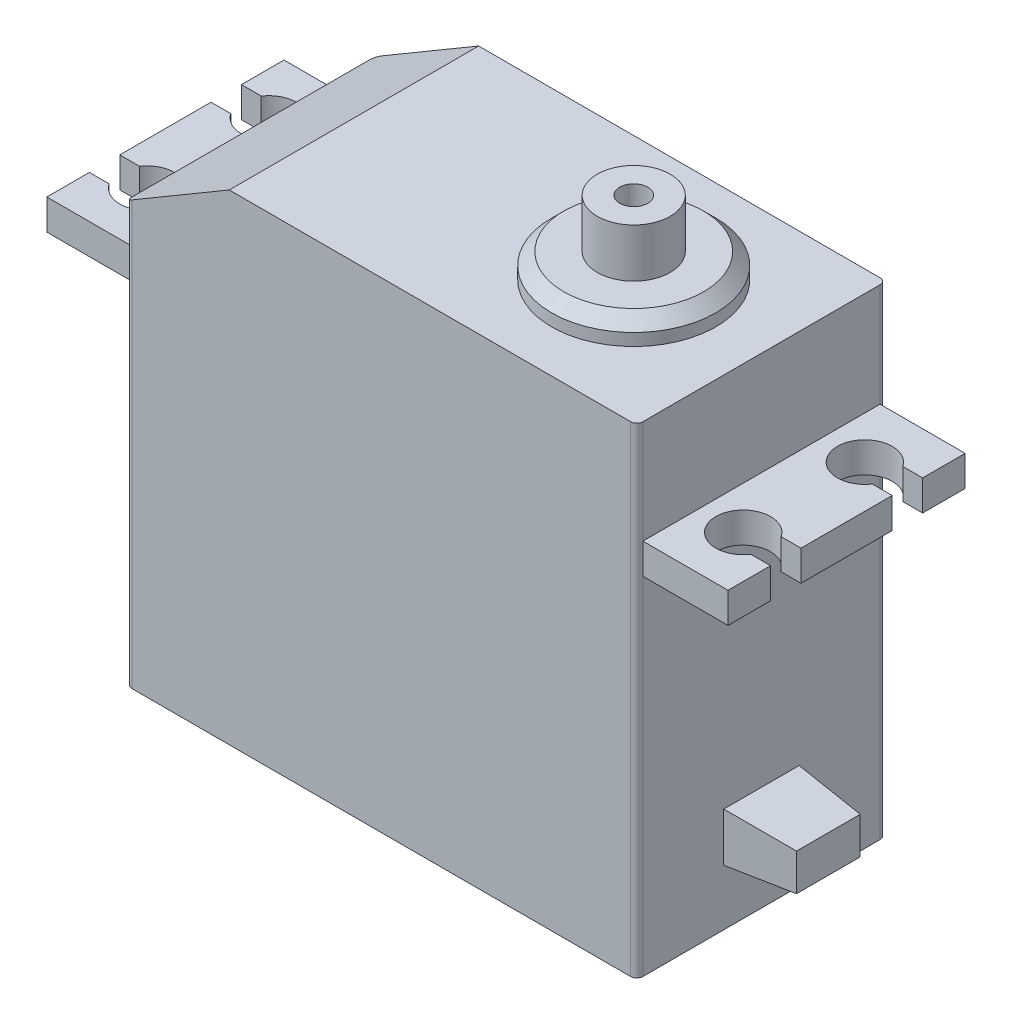
SolidWorks part; units mm, degrees
ref_plane "Front Plane" through (0, 0, 0) normal (0, 0, 1) x (1, 0, 0)
ref_plane "Top Plane" through (0, 0, 0) normal (0, 1, 0) x (1, 0, 0)
ref_plane "Right Plane" through (0, 0, 0) normal (1, 0, 0) x (0, 0, -1)
sketch "Sketch1" plane through (0, 0, 0) normal (0, 1, 0) x (1, 0, 0)
  line L1 (-21, -10.25) -> (21, -10.25)
  line L2 (-21, -10.25) -> (-21, 10.25)
  line L3 (-21, 10.25) -> (21, 10.25)
  line L4 (21, -10.25) -> (21, 10.25)
  point P4 (21, 0)
  point P5 (0, 10.25)
  dimension "D1" = 20.5
  dimension "D2" = 42
extrude "Boss-Extrude1" add sketch "Sketch1" along normal blind 39.5
sketch "Sketch2" plane through (0, 0, 10.25) normal (0, 0, 1) x (1, 0, 0)
  line L0 (-28, 31) -> (28, 31) construction
  line L1 (-21, 39.5) -> (21, 39.5) construction
  line L2 (0, 39.5) -> (0, 0) construction
  line L3 (-21, 0) -> (21, 0) construction
  line L5 (-28, 31) -> (28, 31)
  line L6 (-28, 31) -> (-28, 28.5)
  line L7 (-28, 28.5) -> (28, 28.5)
  line L8 (28, 31) -> (28, 28.5)
  point P8 (0, 31)
  dimension "D1" = 8.5
  dimension "D2" = 56
  dimension "D3" = 2.5
extrude "Boss-Extrude2" add sketch "Sketch2" against normal offset from surface (19.5 mm away) 0.5 from offset 0.5 up to face at (0, 19.75, -10.25) offset against normal yes
sketch "Sketch3" plane through (0, 31, 0) normal (0, 1, 0) x (1, 0, 0)
  line L1 (24.5, 5) -> (-24.5, 5) construction
  line L2 (0, 10.25) -> (0, -10.25) construction
  line L3 (21, 10.25) -> (-21, 10.25) construction
  line L4 (-21, -10.25) -> (21, -10.25) construction
  line L5 (-28, 0) -> (28, 0) construction
  line L6 (-28, 9.75) -> (-28, -9.75) construction
  line L7 (28, 9.75) -> (28, -9.75) construction
  line L8 (26.3708, 3.75) -> (28, 3.75)
  line L10 (26.3708, 6.25) -> (28, 6.25)
  line L11 (28, 3.75) -> (28, 6.25)
  arc A0 (26.3708, 6.25) -> (26.3708, 3.75) centre (24.5, 5) ccw
  circle A1 centre (-24.5, 5) radius 2.25 construction
  point P18 (0, 5)
  dimension "D1" = 4.5
  dimension "D2" = 49
  dimension "D3" = 5
  dimension "D4" = 2.5
extrude "Cut-Extrude1" cut sketch "Sketch3" against normal blind 40
mirror "Mirror1" about plane through (0, 0, 0) normal (0, 0, 1) of "Cut-Extrude1"
mirror "Mirror2" about plane through (0, 0, 0) normal (1, 0, 0) of "Mirror1"
sketch "Sketch4" plane through (0, 0, 10.25) normal (0, 0, 1) x (1, 0, 0)
  line L0 (-21, 34.5) -> (-12.5, 39.5)
  line L1 (-21, 39.5) -> (-21, 0) construction
  line L2 (-21, 39.5) -> (21, 39.5) construction
  line L3 (-21, 34.5) -> (-24.4769, 34.5)
  line L4 (-24.4769, 34.5) -> (-24.4769, 42.3263)
  line L5 (-24.4769, 42.3263) -> (-12.5, 42.3263)
  line L6 (-12.5, 42.3263) -> (-12.5, 39.5)
  line L7 (-21, 31) -> (-28, 31) construction
  dimension "D1" = 3.5
  dimension "D2" = 33.5
extrude "Cut-Extrude2" cut sketch "Sketch4" against normal blind 40
sketch "Sketch5" plane through (0, 39.5, 0) normal (0, 1, 0) x (1, 0, 0)
  line L0 (21, -9.75) -> (21, 9.75) construction
  circle A0 centre (10.5, 0) radius 3
  dimension "D1" = 6
  dimension "D2" = 10.5
extrude "Boss-Extrude3" add sketch "Sketch5" along normal blind 6
sketch "Sketch6" plane through (0, 39.5, 0) normal (0, 1, 0) x (1, 0, 0)
  circle A0 centre (10.5, 0) radius 6.75
  dimension "D1" = 13.5
extrude "Boss-Extrude4" add sketch "Sketch6" along normal blind 2
sketch "Sketch7" plane through (0, 45.5, 0) normal (0, 1, 0) x (1, 0, 0)
  circle A0 centre (10.5, 0) radius 1.15
  dimension "D1" = 2.3
extrude "Cut-Extrude3" cut sketch "Sketch7" against normal blind 5
fillet "Fillet1" radius 0.5 4 edges at (-21, 17.25, -10.25) (21, 19.75, -10.25) (21, 19.75, 10.25) (-21, 17.25, 10.25)
sketch "Sketch8" plane through (21, 0, 0) normal (1, 0, 0) x (0, 0, -1)
  line L0 (-9.75, 0) -> (9.75, 0) construction
  line L1 (-3.1, 4.6) -> (3.1, 4.6)
  line L2 (-3.1, 4.6) -> (-3.1, 8.6)
  line L3 (-3.1, 8.6) -> (3.1, 8.6)
  line L4 (3.1, 4.6) -> (3.1, 8.6)
  point P6 (0, 4.6)
  dimension "D1" = 4
  dimension "D2" = 6.2
  dimension "D3" = 4.6
extrude "Boss-Extrude5" add sketch "Sketch8" along normal blind 5.5 draft 5
chamfer "Chamfer1" distance 1 angle 45 1 edges at (10.5, 41.5, 6.75)
sketch "Sketch9" plane through (0, 39.5, 0) normal (0, 1, 0) x (1, 0, 0)
  line B0 (21, -9.75) -> (21, 9.75)
  line B1 (20.5, 10.25) -> (-12.5, 10.25)
  line B2 (-12.5, -10.25) -> (20.5, -10.25)
  line B3 (-12.5, 10.25) -> (-20.5, 10.25)
  line B4 (-21, 9.75) -> (-21, -9.75)
  line B5 (-20.5, -10.25) -> (-12.5, -10.25)
  line B6 (-28, 9.75) -> (-28, 6.25)
  line B7 (-28, 6.25) -> (-26.3708, 6.25)
  line B8 (-26.3708, 3.75) -> (-28, 3.75)
  line B9 (-28, 3.75) -> (-28, -3.75)
  line B10 (-28, -3.75) -> (-26.3708, -3.75)
  line B11 (-26.3708, -6.25) -> (-28, -6.25)
  line B12 (-28, -6.25) -> (-28, -9.75)
  line B13 (-28, -9.75) -> (-21, -9.75)
  line B14 (-21, -9.75) -> (-21, 9.75)
  line B15 (-21, 9.75) -> (-28, 9.75)
  line B16 (28, -9.75) -> (28, -6.25)
  line B17 (28, -6.25) -> (26.3708, -6.25)
  line B18 (26.3708, -3.75) -> (28, -3.75)
  line B19 (28, -3.75) -> (28, 3.75)
  line B20 (28, 3.75) -> (26.3708, 3.75)
  line B21 (26.3708, 6.25) -> (28, 6.25)
  line B22 (28, 6.25) -> (28, 9.75)
  line B23 (28, 9.75) -> (21, 9.75)
  line B24 (21, 9.75) -> (21, -9.75)
  line B25 (21, -9.75) -> (28, -9.75)
  arc B26 (21, 9.75) -> (20.5, 10.25) centre (20.5, 9.75) ccw
  arc B27 (20.5, -10.25) -> (21, -9.75) centre (20.5, -9.75) ccw
  arc B28 (-20.5, 10.25) -> (-21, 9.75) centre (-20.5, 9.75) ccw
  arc B29 (-21, -9.75) -> (-20.5, -10.25) centre (-20.5, -9.75) ccw
  arc B30 (-26.3708, 3.75) -> (-26.3708, 6.25) centre (-24.5, 5) ccw
  arc B31 (-26.3708, -6.25) -> (-26.3708, -3.75) centre (-24.5, -5) ccw
  arc B32 (26.3708, -3.75) -> (26.3708, -6.25) centre (24.5, -5) ccw
  arc B33 (26.3708, 6.25) -> (26.3708, 3.75) centre (24.5, 5) ccw
  circle B34 centre (10.5, 0) radius 6.75
  circle B35 centre (10.5, 0) radius 5.75
  circle B36 centre (10.5, 0) radius 3
  circle B37 centre (10.5, 0) radius 1.15
sketch_block_instance "Block1-1"
sketch_block "Block1"
